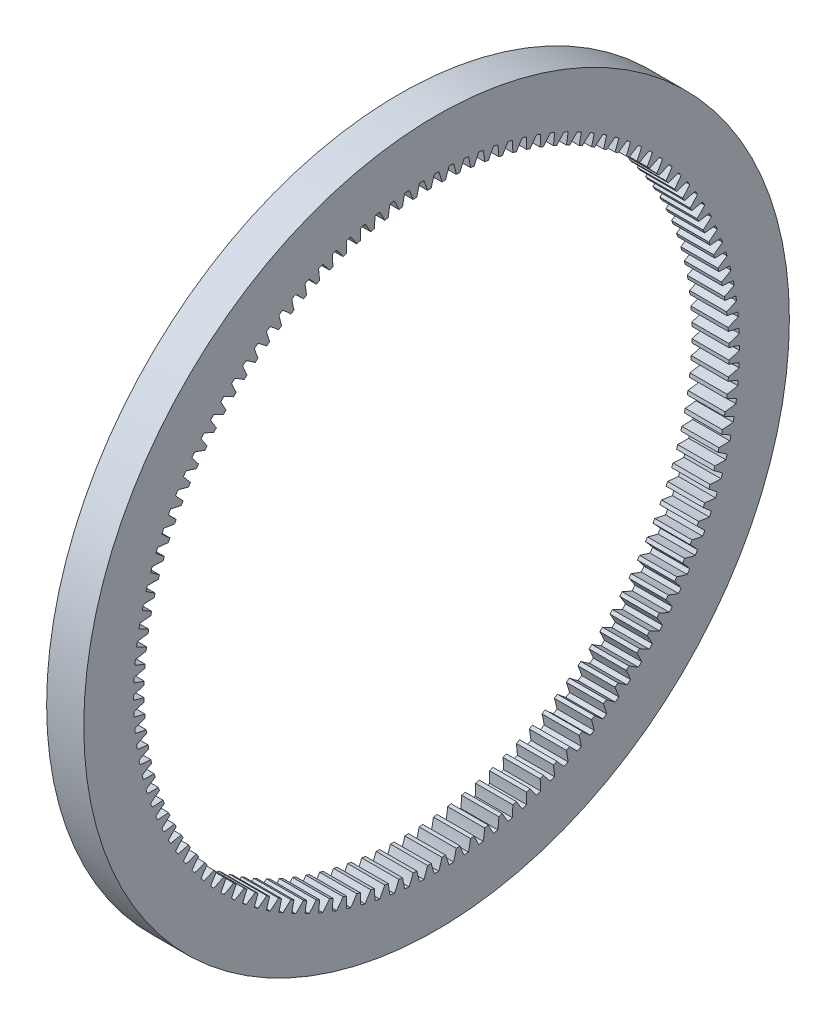
SolidWorks part; units mm, degrees
ref_plane "Plane1" through (0, 0, 0) normal (0, 0, 1) x (1, 0, 0)
ref_plane "Plane2" through (0, 0, 0) normal (0, 1, 0) x (1, 0, 0)
ref_plane "Plane3" through (0, 0, 0) normal (1, 0, 0) x (0, 0, -1)
sketch "HoldingSke" plane through (0, 0, 0) normal (0, 1, 0) x (1, 0, 0)
  line L0 (0, 0) -> (-0.4925, -0.6304)
  line L1 (-15, 0) -> (100, 0) construction
  line L2 (0, 0) -> (-2.1039, 2.3779)
  line L3 (0, 0) -> (-11.863, 4.5341)
  line L4 (0, 0) -> (-5.3169, 6.8053)
  line L5 (0, 0) -> (-23.7986, -8.8762)
  line L6 (0, 0) -> (-10.5278, -7.1032)
  line L7 (-2.1039, 2.3779) -> (3.3635, 27.1825)
  line L8 (-76.2, 3.6279) -> (-54.61, 3.6279)
  line L9 (-67.7845, 28.3722) -> (-49.3413, 33.142)
  line L10 (-76.2, 71.12) -> (104.1128, 71.12)
  line L11 (0, 0) -> (-10, 0)
  line L12 (-76.2, 101.6) -> (-76.155, 101.6)
  line L13 (24.9733, 27.94) -> (52.9518, 28.4284)
  line L14 (24.9733, 27.94) -> (24.9743, 27.94)
  line L15 (24.9733, 27.94) -> (100.4006, 29.5858)
  circle A0 centre (0, 0) radius 95
  circle A1 centre (0, 0) radius 12.7
  circle A2 centre (0, 0) radius 12.7
  dimension "Num_teeth" = 128
  dimension "Pitch_radius" = 180.3128
  dimension "Width" = 10
  dimension "Diameter" = 190
sketch "BasProSke" plane through (0, 0, 0) normal (0, 1, 0) x (1, 0, 0)
  line L0 (-10, 0) -> (60, 0) construction
  line L1 (0, 78.75) -> (0, 95)
  line L2 (0, 78.75) -> (10, 78.75)
  line L3 (10, 78.75) -> (10, 95)
  line L4 (10, 95) -> (0, 95)
  dimension "Thickness" = 10
  dimension "Diameter" = 190
revolve "Base-Revolve" add sketch "BasProSke" angle 360 about L0
sketch "TooCutSke" plane through (0, 0, 0) normal (1, 0, 0) x (0, 0, -1)
  line L3 (1.0942, 79.9925) -> (1.0942, 53.6633) construction
  line L4 (0, 0) -> (0, 59.563) construction
  line L5 (0, 0) -> (-1.6768, 68.3069) construction
  line L6 (-37.3114, 68.8117) -> (36.1207, 70.6143) construction
  circle A0 centre (0, 0) radius 80 construction
  circle A1 centre (0, 0) radius 81.5635 construction
  circle A2 centre (0, 0) radius 69.7066 construction
  circle A3 centre (0, 0) radius 78.7246 construction
  arc A4 (1.4442, 78.7114) -> (0.6023, 81.5613) centre (-37.3114, 68.8117) ccw
  arc A5 (1.4442, 78.7114) -> (-1.4442, 78.7114) centre (0, 0) ccw
  arc A6 (0.6023, 81.5613) -> (-0.6023, 81.5613) centre (0, 0) ccw
  arc A7 (-0.6023, 81.5613) -> (-1.4442, 78.7114) centre (37.3114, 68.8117) ccw
extrude "ToothCut" cut sketch "TooCutSke" along normal through all
fillet "Breaks" [suppressed] radius 0.125
fillet "RootFillets" [suppressed] radius 0.3135
pattern_circular "TeethCuts" count 128 every 2.813 about axis through (-10, 0, 0) along (1, 0, 0) of "RootFillets", "Breaks", "ToothCut"
equation "' \"Module@HoldingSke\" = 6.35"
equation "' \"Num_teeth@HoldingSke\" = 24"
equation "' \"Ap@HoldingSke\" =  14.5"
equation "' \"Ap@HoldingSke\" = 14.5"
equation "' \"Width@HoldingSke\" = 12"
equation "' \"Diameter@HoldingSke\" = 8 * 25.4"
equation "' \"Show_teeth@HoldingSke\" = 100"
equation "' \"Backlash@HoldingSke\" = 0.009 * 25.4"
equation "' \"Addendum_fac@HoldingSke\" = 1.0"
equation "' \"Dedendum_fac@HoldingSke\" = 1.25"
equation "' \"Dedendum_add@HoldingSke\" = 0.00005 * 25.4"
equation "' \"Clearance_fac@HoldingSke\" = 0.25"
equation "\"Pitch@HoldingSke\" = 1 / \"Module@HoldingSke\" "
equation "\"Overcut_dia@TooCutSke\" = (\"Num_teeth@HoldingSke\" - 2 * \"Addendum_fac@HoldingSke\") / \"Pitch@HoldingSke\" - 0.002 * 25.4"
equation "\"Pitch_dia@TooCutSke\" = \"Num_teeth@HoldingSke\" / \"Pitch@HoldingSke\""
equation "\"Base_dia@TooCutSke\" = \"Num_teeth@HoldingSke\" / \"Pitch@HoldingSke\" * cos((\"Ap@HoldingSke\"  * 3.14159265 / 180)) * 0.90"
equation "\"Root_dia@TooCutSke\" = \"Num_teeth@HoldingSke\"  / \"Pitch@HoldingSke\" + 2 *  \"Dedendum_fac@HoldingSke\"/ \"Pitch@HoldingSke\" + \"Dedendum_add@HoldingSke\" * 2"
equation "\"Half_ang@TooCutSke\" = 180 / \"Num_teeth@HoldingSke\""
equation "\"Half_CT@TooCutSke\" = \"Num_teeth@HoldingSke\" / \"Pitch@HoldingSke\" * sin((3.14159265 / 2 / \"Num_teeth@HoldingSke\")) / 2 + 10 * \"Backlash@HoldingSke\" / 4"
equation "\"Flank_rad@TooCutSke\" = \"Num_teeth@HoldingSke\" / \"Pitch@HoldingSke\" / 4"
equation "\"Radius@RootFillets\"= \"Clearance_fac@HoldingSke\" / \"Pitch@HoldingSke\" + \"Dedendum_add@HoldingSke\""
equation "\"Break_rad@Breaks\" = 0.02 / \"Pitch@HoldingSke\" * 5"
equation "\"Num_teeth@TeethCuts\" = int( \"Show_teeth@HoldingSke\" ) + 1"
equation "\"Num_teeth@TeethCuts\" = ((sgn( \"Num_teeth@TeethCuts\" - \"Num_teeth@HoldingSke\" )-1)*( \"Num_teeth@TeethCuts\" - \"Num_teeth@HoldingSke\" ))/-2+ \"Num_teeth@HoldingSke\""
equation "\"Num_teeth@TeethCuts\" = ((sgn( \"Num_teeth@TeethCuts\" - 2.0)+1)*( \"Num_teeth@TeethCuts\" - 2.0))/2 +2.0"
equation "\"Angle@TeethCuts\" = 360.0 / \"Num_teeth@HoldingSke\""
equation "\"Diameter@BasProSke\" = \"Num_teeth@HoldingSke\"  / \"Pitch@HoldingSke\" + 2 *  \"Dedendum_fac@HoldingSke\"/ \"Pitch@HoldingSke\" + \"Dedendum_add@HoldingSke\" * 2 + 0.002 * 25.4"
equation "\"Diameter@BasProSke\" = ((sgn( \"Diameter@BasProSke\"  - \"Diameter@HoldingSke\" )+1)*( \"Diameter@BasProSke\"  - \"Diameter@HoldingSke\" ))/2 + \"Diameter@HoldingSke\""
equation "\"Inside_diameter@BasProSke\" =  (\"Num_teeth@HoldingSke\" - 2 * \"Addendum_fac@HoldingSke\") / \"Pitch@HoldingSke\" "
equation "\"Thickness@BasProSke\"  = \"Width@HoldingSke\""
